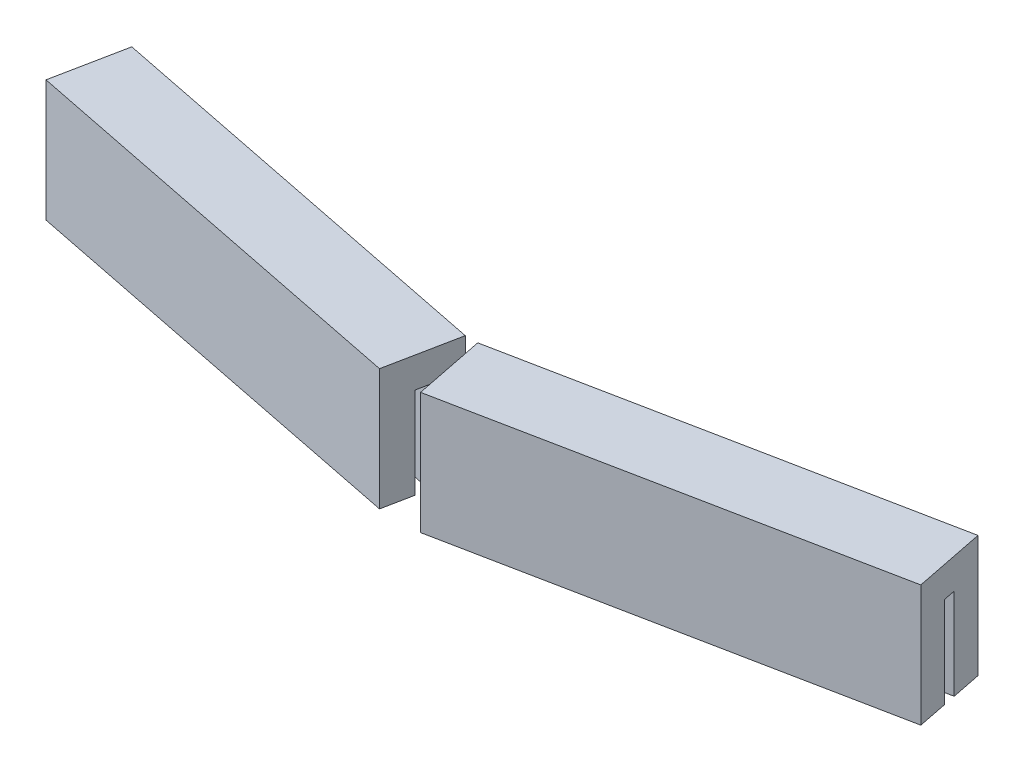
SolidWorks part; units mm, degrees
material "ABS"
ref_plane "Front Plane" through (0, 0, 0) normal (0, 0, 1) x (1, 0, 0)
ref_plane "Top Plane" through (0, 0, 0) normal (0, 1, 0) x (1, 0, 0)
ref_plane "Right Plane" through (0, 0, 0) normal (1, 0, 0) x (0, 0, -1)
ref_axis "X" through (-88.99, 0, 0) along (1, 0, 0)
ref_axis "Y" through (0, 55, 0) along (0, -1, 0)
ref_axis "Z" through (0, 0, -88.99) along (0, 0, 1)
sketch "Sketch1" plane through (0, 0, 0) normal (0, 1, 0) x (1, 0, 0)
  line L0 (27.1702, -94.8196) -> (27.5625, -96.7807) construction
  line L1 (27.1702, -94.8196) -> (27.5625, -96.7807)
  line L2 (22.7661, -96.7807) -> (23.1583, -94.8196) construction
  line L3 (-45.8746, -83.0526) -> (22.7661, -96.7807) construction
  line L4 (22.7661, -96.7807) -> (23.1583, -94.8196)
  line L5 (27.5625, -96.7807) -> (96.2031, -83.0526) construction
  line L6 (23.1583, -94.8196) -> (-45.4823, -81.0914)
  line L7 (-45.4823, -81.0914) -> (-45.8746, -83.0526)
  line L8 (-45.8746, -83.0526) -> (22.7661, -96.7807)
  line L9 (27.1702, -94.8196) -> (95.8109, -81.0914)
  line L10 (95.8109, -81.0914) -> (96.2031, -83.0526)
  line L11 (96.2031, -83.0526) -> (27.5625, -96.7807)
  dimension "D3" = 2
  dimension "D4" = 2
  dimension "D7" = 70
  dimension "D8" = 70
extrude "Boss-Extrude1" add sketch "Sketch1" along normal blind 5
sketch "Sketch2" plane through (0, 5, 0) normal (0, 1, 0) x (1, 0, 0)
  line L0 (0, 0) -> (0, 33.2136) construction
  line L1 (22.9622, -95.8001) -> (-45.6785, -82.072) construction
  line L2 (22.7661, -96.7807) -> (23.1583, -94.8196) construction
  line L3 (-45.4823, -81.0914) -> (-45.8746, -83.0526) construction
  line L4 (-45.4823, -81.0914) -> (-44.5018, -76.1885)
  line L5 (-44.5018, -76.1885) -> (24.1389, -89.9167)
  line L6 (24.1389, -89.9167) -> (23.1583, -94.8196)
  line L7 (23.1583, -94.8196) -> (-45.4823, -81.0914) construction
  line L8 (23.1583, -94.8196) -> (-45.4823, -81.0914)
  line L9 (21.7855, -101.6836) -> (22.7661, -96.7807)
  line L10 (-46.8552, -87.9555) -> (21.7855, -101.6836)
  line L11 (-45.8746, -83.0526) -> (-46.8552, -87.9555)
  line L12 (22.7661, -96.7807) -> (-45.8746, -83.0526)
  line L21 (27.1702, -94.8196) -> (26.1896, -89.9167)
  line L22 (26.1896, -89.9167) -> (94.8303, -76.1885)
  line L23 (94.8303, -76.1885) -> (95.8109, -81.0914)
  line L24 (96.2031, -83.0526) -> (95.8109, -81.0914) construction
  line L25 (95.8109, -81.0914) -> (27.1702, -94.8196) construction
  line L26 (95.8109, -81.0914) -> (27.1702, -94.8196)
  line L27 (27.3663, -95.8001) -> (96.007, -82.072) construction
  line L28 (27.1702, -94.8196) -> (27.5625, -96.7807) construction
  line L29 (97.1837, -87.9555) -> (96.2031, -83.0526)
  line L30 (28.543, -101.6836) -> (97.1837, -87.9555)
  line L31 (27.5625, -96.7807) -> (28.543, -101.6836)
  line L32 (96.2031, -83.0526) -> (27.5625, -96.7807)
  dimension "D1" = 5
  dimension "D2" = 5
extrude "Boss-Extrude2" add sketch "Sketch2" against normal blind 20
